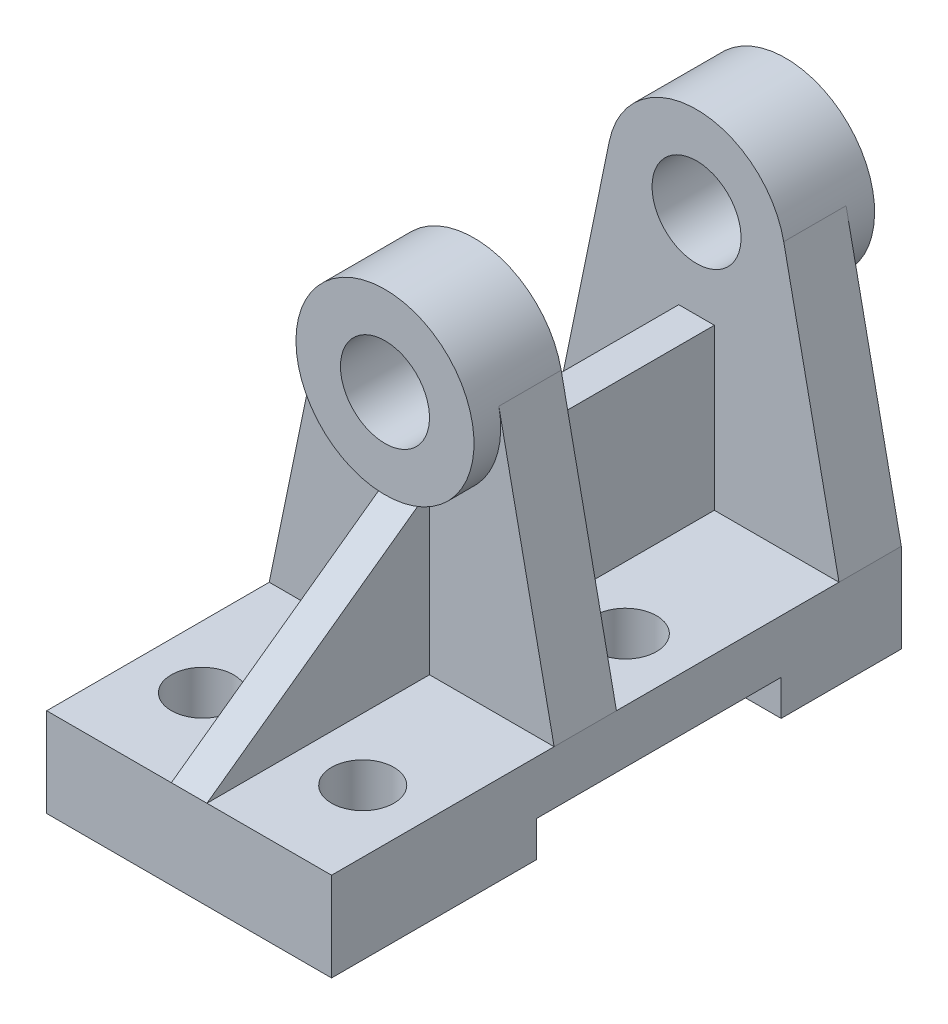
SolidWorks part; units mm, degrees
ref_plane "Front Plane" through (0, 0, 0) normal (0, 0, 1) x (1, 0, 0)
ref_plane "Top Plane" through (0, 0, 0) normal (0, 1, 0) x (1, 0, 0)
ref_plane "Right Plane" through (0, 0, 0) normal (1, 0, 0) x (0, 0, -1)
sketch "Sketch1" plane through (0, 0, 0) normal (0, 1, 0) x (1, 0, 0)
  line L1 (-32, -64) -> (32, -64)
  line L2 (-32, -64) -> (-32, 64)
  line L3 (-32, 64) -> (32, 64)
  line L4 (32, -64) -> (32, 64)
  line L5 (-32, -64) -> (32, 64) construction
  line L6 (-32, 64) -> (32, -64) construction
  point P0 (0, 0)
  dimension "D1" = 64
  dimension "D2" = 128
extrude "Boss-Extrude1" add sketch "Sketch1" along normal blind 20
sketch "Sketch2" plane through (0, 0, -64) normal (0, 0, -1) x (-1, 0, 0)
  line L0 (0, 20) -> (0, 76) construction
  line L2 (-32, 20) -> (32, 20) construction
  line L3 (-32, 20) -> (32, 20)
  line L4 (-32, 20) -> (-19.5858, 80.0491)
  line L5 (0, 0) -> (0, 20) construction
  line L6 (32, 20) -> (19.5858, 80.0491)
  circle A0 centre (0, 76) radius 10
  circle A1 centre (0, 76) radius 20
  line M6 (32, 20) -> (-32, 20)
  dimension "D1" = 20
  dimension "D2" = 40
  dimension "D3" = 56
extrude "Boss-Extrude2" add sketch "Sketch2" against normal blind 14 contours A1 L4 L6 M6 region at (0, 40.0827, -64)
extrude "Boss-Extrude3" add sketch "Sketch2<3>" against normal blind 14 and the other way blind 6 contours A1 A0 region at (0, 95.4343, -64)
sketch "Sketch2<3>" plane through (0, 0, -64) normal (0, 0, -1) x (-1, 0, 0) same geometry as "Sketch2"
sketch "Sketch4" plane through (0, 0, -70) normal (0, 0, -1) x (-1, 0, 0)
  circle A0 centre (0, 76) radius 10 construction
  circle A1 centre (0, 76) radius 20 construction
  circle A2 centre (0, 76) radius 10
  circle A3 centre (0, 76) radius 20
extrude "Boss-Extrude4" add sketch "Sketch4" against normal blind 20 from offset 70 separate body offset against normal yes
sketch "Sketch5" plane through (0, 0, -64) normal (0, 0, -1) x (-1, 0, 0)
  line L0 (32, 20) -> (19.5858, 80.0491) construction
  line L1 (-32, 20) -> (-19.5858, 80.0491) construction
  line L2 (32, 20) -> (19.5858, 80.0491)
  line L3 (-32, 20) -> (-19.5858, 80.0491)
  line L4 (-32, 20) -> (32, 20)
  circle A0 centre (0, 76) radius 20 construction
  arc A1 (-19.5858, 80.0491) -> (19.5858, 80.0491) centre (0, 76) ccw
extrude "Boss-Extrude5" add sketch "Sketch5" along normal blind 14 from offset 78 offset against normal yes
sketch "Sketch8" plane through (0, 0, 0) normal (0, -1, 0) x (1, 0, 0)
  line L0 (0, -9.5) -> (0, 0) construction
  line L1 (-32, -37) -> (32, -37)
  line L2 (-32, -37) -> (-32, 18)
  line L3 (-32, 18) -> (32, 18)
  line L4 (32, -37) -> (32, 18)
  line L5 (-32, -37) -> (32, 18) construction
  line L6 (-32, 18) -> (32, -37) construction
  line L7 (32, -64) -> (-32, -64) construction
  point P0 (0, -9.5)
  dimension "D1" = 27
  dimension "D2" = 55
  dimension "D3" = 64
extrude "Cut-Extrude1" cut sketch "Sketch8" against normal blind 8
ref_axis "Axis1" through (0, 76, 20) along (0, 0, -1)
ref_plane "Plane1" through (0, 0, 0) normal (1, 0, 0) x (0, 0, -1)
sketch "Sketch6" plane through (0, 0, 0) normal (1, 0, 0) x (0, 0, -1)
  line L0 (-64, 20) -> (-14, 20) construction
  line L1 (-64, 20) -> (-14, 20)
  line L2 (-64, 20) -> (-14, 56)
  line L3 (-14, 56) -> (-14, 20)
  line L4 (0, 56) -> (50, 56)
  line L6 (50, 20) -> (50, 80.0491) construction
  line L8 (50, 20) -> (50, 56)
  line L11 (0, 20) -> (50, 20) construction
  line L12 (0, 80.0491) -> (0, 20) construction
  line L13 (0, 20) -> (50, 20)
  line L14 (0, 56) -> (0, 20)
extrude "Boss-Extrude6" add sketch "Sketch6" along normal mid plane 8
sketch "Sketch7" plane through (0, 20, 0) normal (0, 1, 0) x (1, 0, 0)
  line L4 (32, 0) -> (32, 50) construction
  line L5 (4, 50) -> (32, 50) construction
  line L6 (0, 0) -> (0, 50) construction
  line L7 (4, 50) -> (-4, 50) construction
  line L8 (-18, 16) -> (-18, -43) construction
  line L9 (-18, -43) -> (18, -43) construction
  line L10 (-18, 16) -> (18, 16) construction
  line L11 (18, 16) -> (18, -43) construction
  line L13 (4, -64) -> (32, -64) construction
  circle A2 centre (18, 16) radius 7
  circle A4 centre (-18, 16) radius 7
  circle A5 centre (18, -43) radius 7
  circle A6 centre (-18, -43) radius 7
  point P13 (-20, -20)
  dimension "D1" = 14
  dimension "D4" = 21
  dimension "D2" = 14
  dimension "D3" = 34
sketch "Sketch9" plane through (0, 43.5195, 31.334) normal (0, 0.8115, 0.5843) x (1, 0, 0)
  point P0 (-57.5638, 9.988)
extrude "Cut-Extrude2" cut sketch "Sketch7" against normal through all
